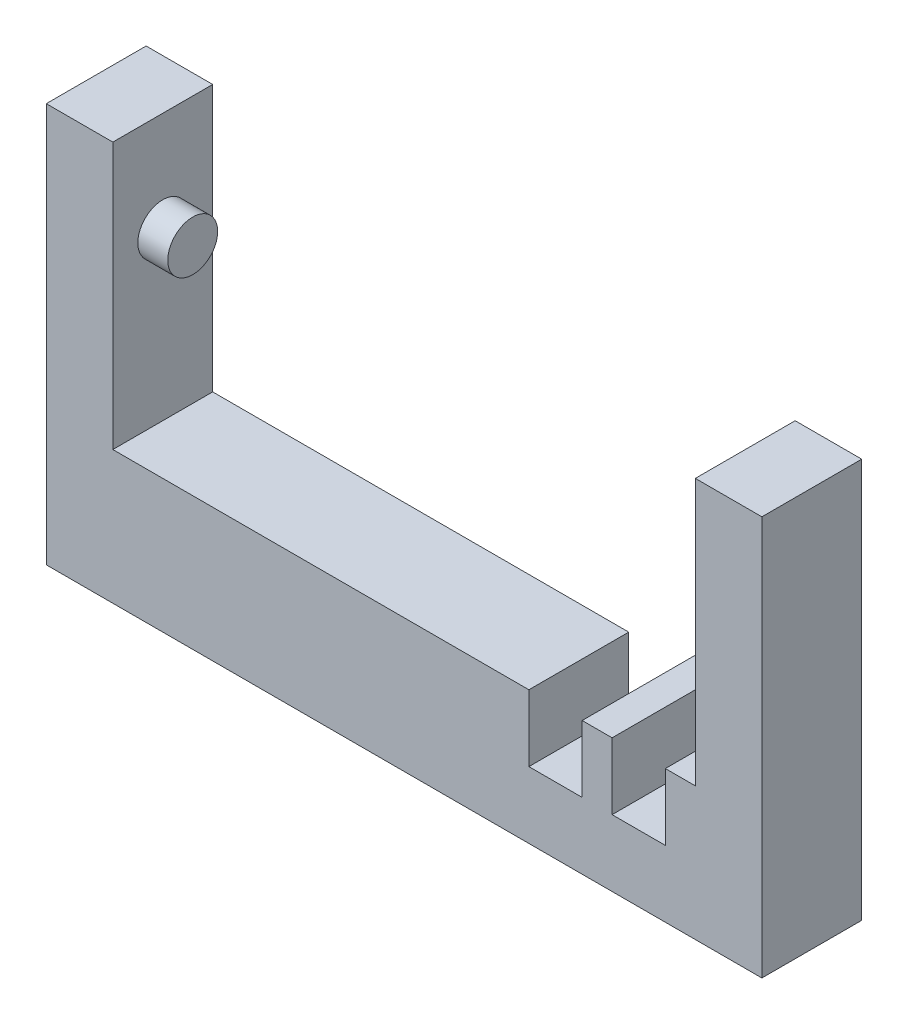
SolidWorks part; units mm, degrees
ref_plane "Front Plane" through (0, 0, 0) normal (0, 0, 1) x (1, 0, 0)
ref_plane "Top Plane" through (0, 0, 0) normal (0, 1, 0) x (1, 0, 0)
ref_plane "Right Plane" through (0, 0, 0) normal (1, 0, 0) x (0, 0, -1)
sketch "Sketch1" plane through (0, 0, 0) normal (0, 1, 0) x (1, 0, 0)
  line L0 (33.5, 7.5) -> (33.5, -7.5)
  line L1 (-41.5, 7.5) -> (41.5, 7.5)
  line L2 (-41.5, 7.5) -> (-41.5, -7.5)
  line L3 (-41.5, -7.5) -> (41.5, -7.5)
  line L4 (41.5, 7.5) -> (41.5, -7.5)
  line L5 (29, 7.5) -> (29, -7.5)
  line L6 (21, 7.5) -> (21, -7.5)
  line L11 (41.5, 7.5) -> (46, 7.5)
  line L12 (46, 7.5) -> (46, -7.5)
  line L13 (46, -7.5) -> (41.5, -7.5)
  line L14 (46, 7.5) -> (56, 7.5)
  line L15 (56, 7.5) -> (56, -7.5)
  line L16 (56, -7.5) -> (46, -7.5)
  line L17 (-41.5, 7.5) -> (-51.5, 7.5)
  line L18 (-51.5, 7.5) -> (-51.5, -7.5)
  line L19 (-51.5, -7.5) -> (-41.5, -7.5)
  point P4 (0, -7.5)
  point P8 (-41.5, 0)
  dimension "D1" = 83
  dimension "D2" = 15
  dimension "D3" = 8
  dimension "D4" = 4.5
  dimension "D5" = 10
  dimension "D6" = 8
  dimension "D7" = 4.5
  dimension "D8" = 10
extrude "Boss-Extrude2" add sketch "Sketch1<3>" along normal blind 10 separate body contours L4 L1 L0 L3 | L1 L6 L3 L5 region at (37.5, 0, 0) region at (25, 0, 0)
sketch "Sketch1<3>" plane through (0, 0, 0) normal (0, 1, 0) x (1, 0, 0) same geometry as "Sketch1"
extrude "Boss-Extrude3" add sketch "Sketch1" along normal blind 20 contours L1 L5 L3 L0 | L6 L1 L2 L3 | L13 L12 L11 L4 region at (31.25, 0, 0) region at (43.75, 0, 0) region at (-10.25, 0, 0)
sketch "Sketch2" plane through (0, 0, -7.5) normal (0, 0, -1) x (-1, 0, 0)
  line L0 (-29, 20) -> (-29, 10) construction
  line L1 (-33.5, 20) -> (-29, 20)
  line L2 (-33.5, 20) -> (-33.5, 15)
  line L3 (-33.5, 15) -> (-29, 15)
  line L4 (-29, 20) -> (-29, 15)
  dimension "D1" = 5
extrude "Boss-Extrude5" add sketch "Sketch2" along normal blind 5
extrude "Boss-Extrude6" add sketch "Sketch1<9>" along normal blind 60 contours L16 L15 L14 L12 | L18 L19 L2 L17 region at (51, 0, 0) region at (-46.5, 0, 0)
sketch "Sketch1<9>" plane through (0, 0, 0) normal (0, 1, 0) x (1, 0, 0) same geometry as "Sketch1"
sketch "Sketch4" plane through (-41.5, 0, 0) normal (1, 0, 0) x (0, 0, -1)
  line L0 (7.5, 60) -> (-7.5, 60) construction
  circle A0 centre (0, 45) radius 3.75
  dimension "D2" = 7.5
  dimension "D1" = 15
extrude "Boss-Extrude7" add sketch "Sketch4" along normal blind 4.5
sketch "Sketch5" plane through (33.5, 0, 0) normal (1, 0, 0) x (0, 0, -1)
  line L0 (12.5, 15) -> (7.5, 15) construction
  line L1 (12.5, 20) -> (12.5, 15) construction
  circle A0 centre (10, 17.5) radius 1.5
  point P4 (10, 15)
  point P7 (12.5, 17.5)
  dimension "D1" = 3
extrude "Cut-Extrude1" cut sketch "Sketch5" against normal blind 5
